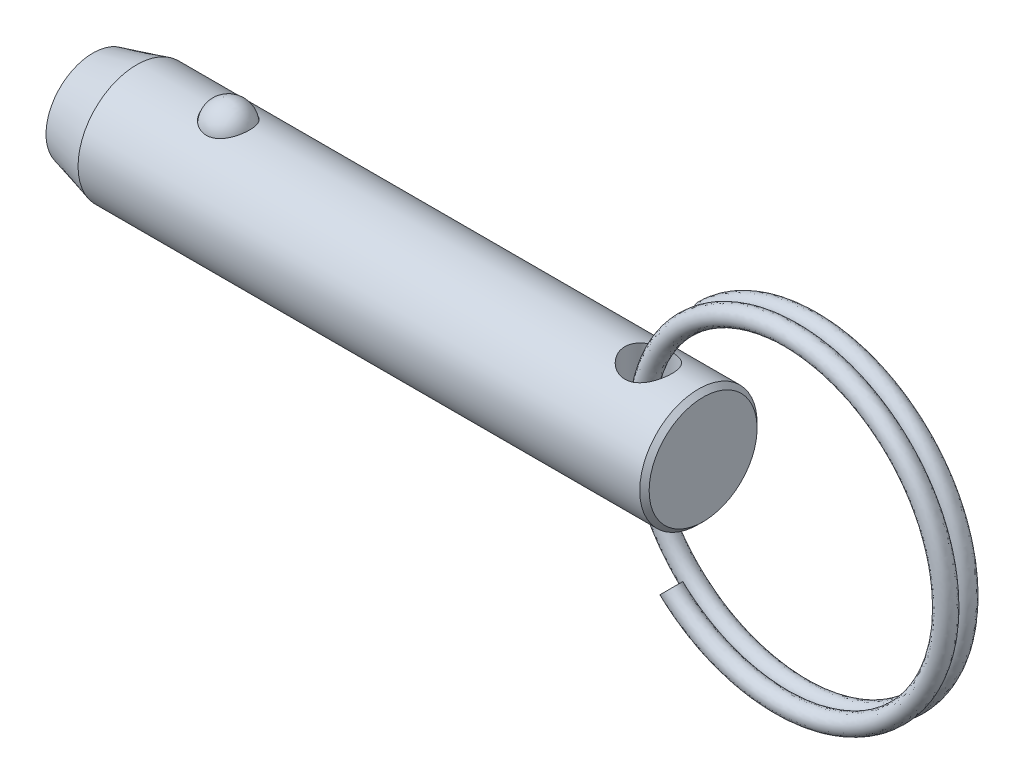
SolidWorks part; units mm, degrees
material "Plain Carbon Steel"
ref_plane "Front" through (0, 0, 0) normal (0, 0, 1) x (1, 0, 0)
ref_plane "Top" through (0, 0, 0) normal (0, 1, 0) x (1, 0, 0)
ref_plane "Right" through (0, 0, 0) normal (1, 0, 0) x (0, 0, -1)
sketch "Sketch1" plane through (0, 0, 0) normal (0, 0, 1) x (1, 0, 0)
  line L0 (24.765, 4.3815) -> (24.384, 4.7625)
  line L1 (24.384, 4.7625) -> (24.765, 4.7625) construction
  line L4 (24.765, 4.3815) -> (24.765, 0)
  line L5 (24.765, 4.7625) -> (24.765, 4.3815) construction
  line L16 (24.384, 4.7625) -> (-21.2102, 4.7625)
  line L17 (-24.765, 4.7625) -> (-24.765, 3.81) construction
  line L19 (-21.2102, 4.7625) -> (-24.765, 4.7625) construction
  line L22 (-24.765, -4.7625) -> (-21.2102, -4.7625) construction
  line L23 (-13.7714, 4.2863) -> (-13.7714, -4.2863) construction
  line L24 (-24.765, 0) -> (24.765, 0)
  line L27 (24.765, 0) -> (29.1465, 0) construction
  line L29 (-24.765, 0) -> (-24.765, -3.81) construction
  line L36 (18.415, 0) -> (18.415, 4.7625) construction
  line L37 (-24.765, 3.81) -> (-24.765, 0)
  line L38 (-21.2102, -4.7625) -> (24.765, -4.7625) construction
  line L39 (-24.765, -3.81) -> (-24.765, -4.7625) construction
  line L40 (-21.2102, 4.7625) -> (-24.765, 3.81)
  line L42 (-21.2102, -4.7625) -> (-24.765, -3.81) construction
  line L43 (-21.2102, 4.7625) -> (-21.2102, -4.7625) construction
  circle A2 centre (-13.7714, 4.2863) radius 1.7716 construction
  point P35 (-12.065, 4.7625)
  dimension "A1" = 15
revolve "Revolve1" add sketch "Sketch1" angle 360 about L27
sketch "Sketch2" plane through (0, 0, 0) normal (0, 0, 1) x (1, 0, 0)
  line L0 (-11.9744, 4.2862) -> (-15.5685, 4.2862)
  line L1 (-13.7714, 6.0579) -> (-13.7714, 6.0833) construction
  line L2 (-11.9744, 4.2862) -> (-8.3803, 4.2862) construction
  circle A0 centre (-13.7714, 4.2863) radius 1.7716 construction
  circle A1 centre (-13.7714, 4.2863) radius 1.7716 construction
  arc A2 (-15.5685, 4.2862) -> (-11.9744, 4.2862) centre (-13.7714, 4.2863) cw
  dimension "D1" = 0.0254
revolve "Cut-Revolve1" cut sketch "Sketch2" angle 360 about L2
sketch "Sketch3" plane through (0, 0, 0) normal (0, 0, 1) x (1, 0, 0)
  line L0 (-11.9998, 4.2863) -> (-15.5431, 4.2863)
  line L1 (-11.9998, 4.2863) -> (-8.4565, 4.2863) construction
  circle A0 centre (-13.7714, 4.2863) radius 1.7716 construction
  arc A1 (-11.9998, 4.2863) -> (-15.5431, 4.2863) centre (-13.7714, 4.2863) ccw
revolve "Revolve2" add sketch "Sketch3" angle 360 about L1
sketch "Sketch4" plane through (0, 0, 0) normal (0, 0, 1) x (1, 0, 0)
  line L1 (20.32, -4.7625) -> (22.225, -4.7625)
  line L2 (20.32, -4.7625) -> (20.32, 4.7625)
  line L3 (20.32, 4.7625) -> (22.225, 4.7625)
  line L4 (22.225, -4.7625) -> (22.225, 4.7625)
  line L5 (20.32, -4.7625) -> (20.32, -6.6675) construction
  line L6 (22.225, 4.7625) -> (24.765, 4.7625) construction
  line L8 (18.415, -4.7625) -> (18.415, 4.7625) construction
  line L9 (18.415, 0) -> (20.32, 0) construction
  line L11 (20.32, 0) -> (22.225, 0) construction
  line L12 (24.384, 4.7625) -> (-21.2102, 4.7625) construction
  line L14 (-21.2102, -4.7625) -> (24.765, -4.7625) construction
  dimension "D1" = 3.81
revolve "Cut-Revolve2" cut sketch "Sketch4" angle 360 about L2
sketch "Sketch5" plane through (0, 0, 0) normal (0, 0, 1) x (1, 0, 0)
  line L0 (0, 0) -> (19.0624, 0) construction
  line L1 (19.0624, 0) -> (19.0624, 4.7625) construction
  line L2 (24.384, 4.7625) -> (-21.2102, 4.7625) construction
  line L3 (32.5244, 0) -> (45.9864, 0) construction
  line L4 (22.225, 4.7625) -> (21.5776, 4.7625) construction
  line L5 (20.32, 4.7625) -> (22.225, 4.7625) construction
  line L6 (19.933, 4.7625) -> (19.933, -4.7625) construction
  line L7 (19.0624, 4.7625) -> (18.415, 4.7625) construction
  line L8 (20.32, -4.7625) -> (22.225, -4.7625) construction
  line L9 (19.933, -4.7625) -> (22.225, -4.7625) construction
  line L10 (19.0624, 0) -> (32.5244, 0) construction
  line L12 (21.5776, 4.7625) -> (19.933, 4.7625) construction
  line L13 (32.5244, 11.938) -> (32.5244, 13.462) construction
  circle A0 centre (32.5244, 0) radius 13.462
  circle A1 centre (32.5244, 0) radius 11.938 construction
  circle A2 centre (32.5244, 0) radius 12.7 construction
  point P26 (32.5244, 12.7)
curve "Helix/Spiral1" pitch 1.5494 height 1.3557 radius 13.462 left hand yes centre (32.5244, 0, 0) axis (0, 0, -1) start towards (1, 0, 0)
sketch "Sketch6" plane through (114.0038, 0, 0) normal (0, 1, 0) x (0, 0, -1)
  line L0 (0, 93.4174) -> (0, 94.1794) construction
  line L1 (0, 94.1794) -> (0, 94.9414) construction
  circle A0 centre (0, 94.1794) radius 0.762
  dimension "D1" = 1.524
sketch "Sketch7" plane through (0, 0, 0) normal (0, 0, 1) x (1, 0, 0)
  circle A0 centre (32.5244, 0) radius 13.462 construction
  circle A1 centre (32.5244, 0) radius 13.462
curve "Helix/Spiral2" pitch 1.5494 height 1.3557 radius 13.462 left hand yes centre (32.5244, 0, 0) axis (0, 0, 1) start towards (1, 0, 0)
sweep "Sweep1" add profiles "Sketch6" path "Helix/Spiral1"
sweep "Sweep2" add profiles "Sketch6<2>" path "Helix/Spiral2"
sketch "Sketch6<2>" plane through (114.0038, 0, 0) normal (0, 1, 0) x (0, 0, -1) same geometry as "Sketch6"
equation "\"D12@Sketch1\"=\"A@Sketch1\" * 0.80"
equation "\"D2@Sketch1\"=\"A@Sketch1\" * 0.9"
equation "\"D1@Sketch4\" = \"A@Sketch1\" / 2.5"
equation "\"Ring OD@Sketch5\" = \"R Ring Dia@Sketch5\" * 0.06"
equation "\"D4@Helix/Spiral1\"=\"Ring OD@Sketch5\" + 0.001"
equation "\"D1@Sketch6\"=\"Ring OD@Sketch5\""
equation "\"D4@Helix/Spiral2\" = \"D4@Helix/Spiral1\""
equation "\"D5@Helix/Spiral2\" = \"D5@Helix/Spiral1\""
